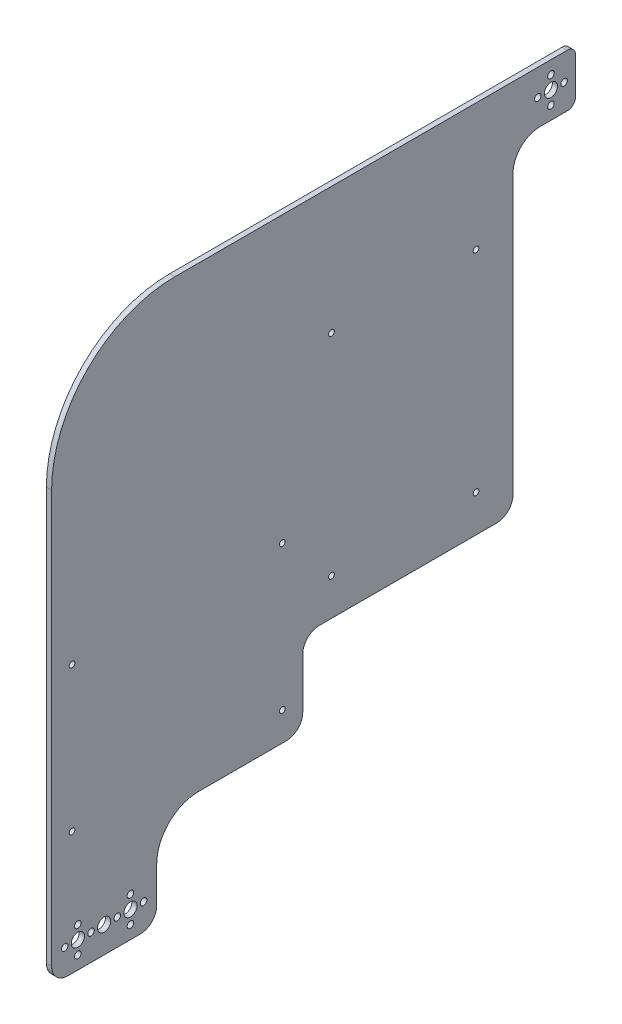
SolidWorks part; units mm, degrees
ref_plane "Front" through (0, 0, 0) normal (0, 0, 1) x (1, 0, 0)
ref_plane "Top" through (0, 0, 0) normal (0, 1, 0) x (1, 0, 0)
ref_plane "Right" through (0, 0, 0) normal (1, 0, 0) x (0, 0, -1)
sketch "Sketch1" plane through (0, 0, 0) normal (1, 0, 0) x (0, 0, -1)
  line L0 (-248, -304) -> (-264, -304) construction
  line L1 (-272, -300) -> (-272, -308) construction
  line L2 (-240, -288) -> (-240, -310)
  line L3 (-250, -320) -> (-294, -320)
  line L4 (-304, -310) -> (-304, -288)
  line L5 (-16, 16) -> (10, 16)
  line L6 (15, 11) -> (15, -11)
  line L7 (10, -16) -> (-6.55, -16)
  line L8 (-240, -288) -> (-6.55, -16) construction
  line L9 (-229, 16) -> (-16, 16)
  line L10 (-304, -288) -> (-304, -59)
  line L11 (-151.1, -252.6) -> (-151.1, -221.8)
  line L12 (-141.1, -211.8) -> (-33.1, -211.8)
  line L13 (-23.1, -201.8) -> (-23.1, -32.55)
  line L14 (-214.6, -262.6) -> (-161.1, -262.6)
  line L15 (-6.55, -16) -> (-23.1, -16) construction
  line L16 (-227.55, -157.1) -> (-227.55, -245.1) construction
  circle A0 centre (-256, -304) radius 4
  circle A1 centre (0, 0) radius 4
  circle A2 centre (8, 0) radius 2
  circle A3 centre (0, -8) radius 2
  circle A4 centre (-8, 0) radius 2
  circle A5 centre (0, 8) radius 2
  circle A6 centre (-248, -304) radius 2
  circle A7 centre (-256, -312) radius 2
  circle A8 centre (-264, -304) radius 2 [skipped]
  circle A9 centre (-256, -296) radius 2
  circle A10 centre (-264, -304) radius 2
  circle A11 centre (-272, -304) radius 4
  circle A12 centre (-288, -312) radius 2
  circle A13 centre (-280, -304) radius 2
  circle A14 centre (-288, -296) radius 2
  circle A15 centre (-288, -304) radius 4
  circle A16 centre (-296, -304) radius 2
  arc A17 (-240, -310) -> (-250, -320) centre (-250, -310) cw
  arc A18 (-294, -320) -> (-304, -310) centre (-294, -310) cw
  arc A19 (10, 16) -> (15, 11) centre (10, 11) cw
  arc A20 (15, -11) -> (10, -16) centre (10, -11) cw
  arc A21 (-304, -59) -> (-229, 16) centre (-229, -59) cw
  arc A22 (-240, -288) -> (-214.6, -262.6) centre (-214.6, -288) cw
  arc A23 (-6.55, -16) -> (-23.1, -32.55) centre (-6.55, -32.55) ccw
  arc A24 (-33.1, -211.8) -> (-23.1, -201.8) centre (-33.1, -201.8) ccw
  arc A25 (-151.1, -252.6) -> (-161.1, -262.6) centre (-161.1, -252.6) cw
  arc A26 (-151.1, -221.8) -> (-141.1, -211.8) centre (-141.1, -221.8) cw
  point P18 (0, 0)
  point P27 (-256, -304)
  point P47 (-272, -320)
  point P58 (15, 0)
  point P75 (-151.1, -262.6)
  point P78 (-151.1, -211.8)
  point P79 (-227.55, -166.2407)
  line B0 (-133.6, -61.3) -> (-133.6, -189.3) construction
  line B1 (-141.1, -196.8) -> (-38.1, -196.8) construction
  line B2 (-38.1, -53.8) -> (-38.1, -196.8) construction
  circle B3 centre (-133.6, -61.3) radius 1.75
  circle B4 centre (-45.6, -61.3) radius 1.75
  circle B5 centre (-45.6, -189.3) radius 1.75
  circle B6 centre (-133.6, -189.3) radius 1.75
  line B7 (-299.05, -252.6) -> (-156.05, -252.6) construction
  line B8 (-156.05, -252.6) -> (-156.05, -149.6) construction
  line B9 (-299.05, -149.6) -> (-156.05, -149.6) construction
  line B10 (-163.55, -245.1) -> (-163.55, -157.1) construction
  circle B11 centre (-291.55, -245.1) radius 1.75
  circle B12 centre (-291.55, -157.1) radius 1.75
  circle B13 centre (-163.55, -157.1) radius 1.75
  circle B14 centre (-163.55, -245.1) radius 1.75
  dimension "D1" = 8
  dimension "D4" = 4
  dimension "D14" = 10
  dimension "D15" = 5
  dimension "D19" = 75
  dimension "D24" = 10
  dimension "D2" = 256
  dimension "D3" = 304
  dimension "D5" = 8
  dimension "D7" = 8
  dimension "D10" = 16
  dimension "D11" = 16
  dimension "D12" = 16
  dimension "D13" = 16
  dimension "D16" = 15
  dimension "D17" = 16
  dimension "D18" = 16
  dimension "D20" = 88.9
  dimension "D21" = 25.4
  dimension "D22" = 50.8
  dimension "D23" = 38.1
  dimension "D25" = 15
  dimension "D26" = 15
  dimension "D27" = 10
  dimension "D9" = 2
  dimension "D6" = 4
  dimension "D8" = 4
sketch_block_instance "Expansion Hub Mounting Holes-1"
sketch_block "Expansion Hub Mounting Holes" parameters "D1"=3.5, "D2"=143, "D3"=103
sketch_block_instance "Expansion Hub Mounting Holes-5"
extrude "Boss-Extrude1" add sketch "Sketch1" against normal blind 3.175
